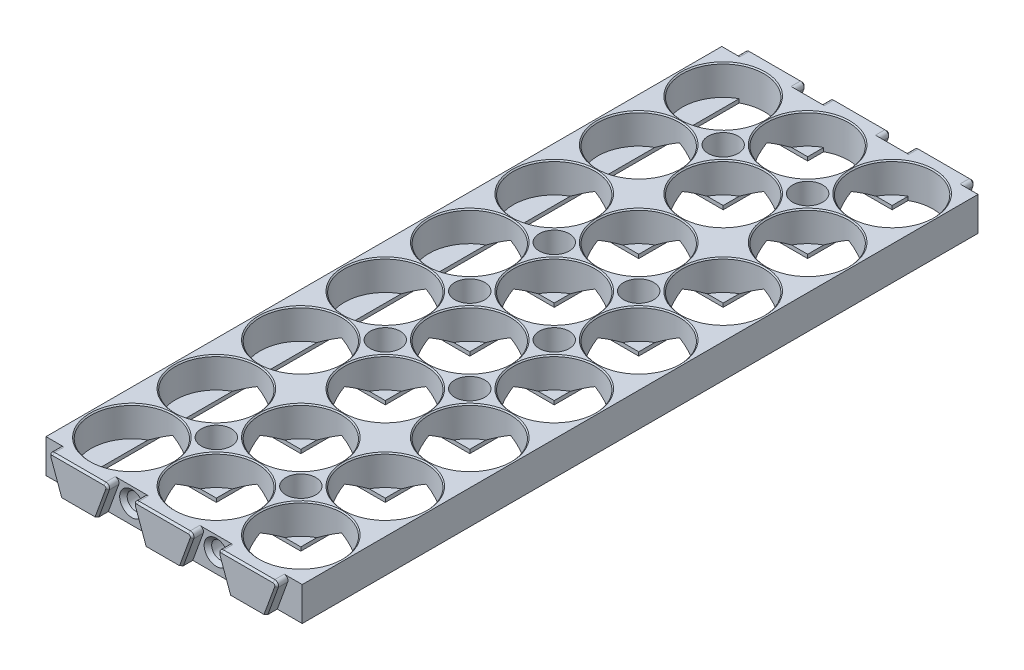
SolidWorks part; units mm, degrees
ref_plane "Front Plane" through (0, 0, 0) normal (0, 0, 1) x (1, 0, 0)
ref_plane "Top Plane" through (0, 0, 0) normal (0, 1, 0) x (1, 0, 0)
ref_plane "Right Plane" through (0, 0, 0) normal (1, 0, 0) x (0, 0, -1)
sketch "Sketch1" plane through (0, 0, 0) normal (0, 1, 0) x (1, 0, 0)
  line L0 (-11.25, 10.875) -> (11.25, 10.875) construction
  line L1 (-11.25, -11.25) -> (11.25, -11.25)
  line L2 (-11.25, -11.25) -> (-11.25, 11.25)
  line L3 (-11.25, 11.25) -> (11.25, 11.25)
  line L4 (11.25, -11.25) -> (11.25, 11.25)
  line L5 (-11.25, -11.25) -> (11.25, 11.25) construction
  line L6 (-11.25, 11.25) -> (11.25, -11.25) construction
  circle A0 centre (0, 0) radius 10.875
  point P0 (0, 0)
  dimension "D1" = 21.75
  dimension "D2" = 22.5
  dimension "D3" = 0.375
extrude "Boss-Extrude1" add sketch "Sketch1" along normal blind 8
sketch "Sketch2" plane through (0, 0, 0) normal (0, -1, 0) x (1, 0, 0)
  line L0 (5.25, 11.25) -> (-5.25, 11.25) construction
  line L1 (11.25, 11.25) -> (5.25, 11.25)
  line L2 (11.25, 11.25) -> (11.25, 5.25)
  line L3 (11.25, 5.25) -> (5.25, 5.25)
  line L4 (5.25, 11.25) -> (5.25, 5.25)
  line L5 (11.25, -11.25) -> (5.25, -11.25)
  line L6 (11.25, -11.25) -> (11.25, -5.25)
  line L7 (11.25, -5.25) -> (5.25, -5.25)
  line L8 (5.25, -11.25) -> (5.25, -5.25)
  line L9 (-11.25, -11.25) -> (-5.25, -11.25)
  line L10 (-11.25, -11.25) -> (-11.25, -5.25)
  line L11 (-11.25, -5.25) -> (-5.25, -5.25)
  line L12 (-5.25, -11.25) -> (-5.25, -5.25)
  line L13 (-11.25, 11.25) -> (-5.25, 11.25)
  line L14 (-11.25, 11.25) -> (-11.25, 5.25)
  line L15 (-11.25, 5.25) -> (-5.25, 5.25)
  line L16 (-5.25, 11.25) -> (-5.25, 5.25)
  line L17 (11.25, 5.25) -> (11.25, -5.25) construction
  line L18 (5.25, -11.25) -> (-5.25, -11.25) construction
  line L19 (-11.25, 5.25) -> (-11.25, -5.25) construction
  dimension "D1" = 10.5
extrude "Boss-Extrude2" add sketch "Sketch2" along normal blind 1
chamfer "Chamfer2" distance 0.3 angle 45 1 edges at (0, 8, 10.875)
pattern_linear "LPattern1" count 8 spacing 22.5 along (0, 0, 1) count 3 spacing 22.5 along (1, 0, 0) of "Boss-Extrude2", "Boss-Extrude1", "Chamfer2"
sketch "Sketch5" plane through (0, 0, -5.25) normal (0, 0, 1) x (1, 0, 0)
  line L25 (-5.25, -1) -> (-5.25, 0) construction
  line L26 (-5.25, -1) -> (-11.25, -1) construction
  line L27 (-11.25, -1) -> (-11.25, 0) construction
  line L29 (-5.25, 0) -> (-9.5238, 0) construction
  line L35 (-5.25, -1) -> (-5.25, 0)
  line L36 (-5.25, -1) -> (-11.25, -1)
  line L37 (-11.25, -1) -> (-11.25, 0)
  line L39 (-5.25, 0) -> (-11.25, 0)
  line L55 (56.25, -1) -> (50.25, -1)
  line L56 (56.25, -1) -> (56.25, 0)
  line L57 (56.25, 0) -> (50.25, 0)
  line L58 (50.25, -1) -> (50.25, 0)
  dimension "D1" = 6
extrude "Boss-Extrude3" add sketch "Sketch5" along normal up to surface (174 mm away)
sketch "Sketch6" plane through (0, 0, 0) normal (0, -1, 0) x (1, 0, 0)
  line L27 (39.75, -11.25) -> (50.25, -11.25) construction
  line L28 (50.25, -11.25) -> (50.25, -9.5238) construction
  line L29 (39.75, -9.5238) -> (39.75, -11.25) construction
  line L30 (17.25, -9.5238) -> (17.25, -11.25) construction
  line L31 (17.25, -11.25) -> (27.75, -11.25) construction
  line L32 (27.75, -11.25) -> (27.75, -9.5238) construction
  line L33 (-5.25, -9.5238) -> (-5.25, -11.25) construction
  line L34 (-5.25, -11.25) -> (5.25, -11.25) construction
  line L35 (5.25, -11.25) -> (5.25, -9.5238) construction
  line L51 (39.75, -11.25) -> (50.25, -11.25)
  line L52 (50.25, -11.25) -> (50.25, -9.5238)
  line L53 (39.75, -9.5238) -> (39.75, -11.25)
  line L54 (17.25, -9.5238) -> (17.25, -11.25)
  line L55 (17.25, -11.25) -> (27.75, -11.25)
  line L56 (27.75, -11.25) -> (27.75, -9.5238)
  line L57 (-5.25, -9.5238) -> (-5.25, -11.25)
  line L58 (-5.25, -11.25) -> (5.25, -11.25)
  line L59 (5.25, -11.25) -> (5.25, -9.5238)
  line L84 (5.25, 168.75) -> (-5.25, 168.75) construction
  line L85 (-5.25, 168.75) -> (-5.25, 167.0238) construction
  line L86 (5.25, 167.0238) -> (5.25, 168.75) construction
  line L87 (27.75, 167.0238) -> (27.75, 168.75) construction
  line L88 (27.75, 168.75) -> (17.25, 168.75) construction
  line L89 (17.25, 168.75) -> (17.25, 167.0238) construction
  line L93 (50.25, 167.0238) -> (50.25, 168.75) construction
  line L94 (50.25, 168.75) -> (39.75, 168.75) construction
  line L95 (39.75, 168.75) -> (39.75, 167.0238) construction
  line L96 (5.25, 168.75) -> (-5.25, 168.75)
  line L97 (-5.25, 168.75) -> (-5.25, 167.0238)
  line L98 (5.25, 167.0238) -> (5.25, 168.75)
  line L99 (27.75, 167.0238) -> (27.75, 168.75)
  line L100 (27.75, 168.75) -> (17.25, 168.75)
  line L101 (17.25, 168.75) -> (17.25, 167.0238)
  line L105 (50.25, 167.0238) -> (50.25, 168.75)
  line L106 (50.25, 168.75) -> (39.75, 168.75)
  line L107 (39.75, 168.75) -> (39.75, 167.0238)
  arc A9 (39.75, -9.5238) -> (50.25, -9.5238) centre (45, 0) ccw construction
  arc A10 (17.25, -9.5238) -> (27.75, -9.5238) centre (22.5, 0) ccw construction
  arc A11 (-5.25, -9.5238) -> (5.25, -9.5238) centre (0, 0) ccw construction
  arc A17 (39.75, -9.5238) -> (50.25, -9.5238) centre (45, 0) ccw
  arc A18 (17.25, -9.5238) -> (27.75, -9.5238) centre (22.5, 0) ccw
  arc A19 (-5.25, -9.5238) -> (5.25, -9.5238) centre (0, 0) ccw
  arc A28 (5.25, 167.0238) -> (-5.25, 167.0238) centre (0, 157.5) ccw construction
  arc A29 (27.75, 167.0238) -> (17.25, 167.0238) centre (22.5, 157.5) ccw construction
  arc A31 (50.25, 167.0238) -> (39.75, 167.0238) centre (45, 157.5) ccw construction
  arc A32 (5.25, 167.0238) -> (-5.25, 167.0238) centre (0, 157.5) ccw
  arc A33 (27.75, 167.0238) -> (17.25, 167.0238) centre (22.5, 157.5) ccw
  arc A35 (50.25, 167.0238) -> (39.75, 167.0238) centre (45, 157.5) ccw
extrude "Boss-Extrude4" add sketch "Sketch6" along normal up to surface (1 mm away) up to face at (-8.25, -1, 78.75)
sketch "Sketch7" plane through (0, 0, 0) normal (0, 0, 1) x (1, 0, 0)
  line L0 (-11.25, 8) -> (56.25, 8) construction
  line L1 (-5.25, 0) -> (5.25, 0)
  line L2 (-5.25, 0) -> (0, 5.25) construction
  line L3 (0, 5.25) -> (5.25, 0) construction
  line L4 (0, 0) -> (0, 8) construction
  line L6 (-5.25, 0) -> (0, 3.0311)
  line L7 (0, 3.0311) -> (5.25, 0)
  line L9 (-5.25, -1) -> (-5.25, 0) construction
  line L10 (5.25, -1) -> (5.25, 0) construction
  line L11 (-5.25, -1) -> (-5.25, 0) construction
  line L12 (5.25, -1) -> (5.25, 0) construction
  line L13 (17.25, 0) -> (22.5, 3.0311)
  line L14 (22.5, 3.0311) -> (27.75, 0)
  line L15 (17.25, 0) -> (27.75, 0)
  line L16 (39.75, 0) -> (45, 3.0311)
  line L17 (45, 3.0311) -> (50.25, 0)
  line L18 (39.75, 0) -> (50.25, 0)
  line L22 (-5.25, 0) -> (17.25, 0) construction
  dimension "D1" = 45
  dimension "D2" = 30
  dimension "D3" = 4.9689
  dimension "D5" = 22.5
  dimension "D4" = 3
extrude "Cut-Extrude1" cut sketch "Sketch7" along normal up to surface (152.25 mm away) up to face at (33.75, -0.3333, 152.25)
sketch "Sketch16" plane through (0, 0, 0) normal (1, 0, 0) x (0, 0, -1)
  line L2 (-5.25, -1) -> (-5.25, 0) construction
  line L3 (5.25, -1) -> (5.25, 0) construction
  line L4 (-5.25, 0) -> (0, 3.0311)
  line L5 (0, 3.0311) -> (5.25, 0)
  line L6 (-5.25, 0) -> (5.25, 0)
  line L7 (-5.25, -1) -> (-5.25, 0) construction
  line L8 (5.25, -1) -> (5.25, 0) construction
  line L9 (-22.5, 3.0311) -> (-17.25, 0)
  line L10 (-27.75, 0) -> (-17.25, 0)
  line L11 (-27.75, 0) -> (-22.5, 3.0311)
  line L12 (-45, 3.0311) -> (-39.75, 0)
  line L13 (-50.25, 0) -> (-39.75, 0)
  line L14 (-50.25, 0) -> (-45, 3.0311)
  line L15 (-67.5, 3.0311) -> (-62.25, 0)
  line L16 (-72.75, 0) -> (-62.25, 0)
  line L17 (-72.75, 0) -> (-67.5, 3.0311)
  line L18 (-90, 3.0311) -> (-84.75, 0)
  line L19 (-95.25, 0) -> (-84.75, 0)
  line L20 (-95.25, 0) -> (-90, 3.0311)
  line L21 (-112.5, 3.0311) -> (-107.25, 0)
  line L22 (-117.75, 0) -> (-107.25, 0)
  line L23 (-117.75, 0) -> (-112.5, 3.0311)
  line L24 (-135, 3.0311) -> (-129.75, 0)
  line L25 (-140.25, 0) -> (-129.75, 0)
  line L26 (-140.25, 0) -> (-135, 3.0311)
  line L27 (-157.5, 3.0311) -> (-152.25, 0)
  line L28 (-162.75, 0) -> (-152.25, 0)
  line L29 (-162.75, 0) -> (-157.5, 3.0311)
  line L42 (0, 3.0311) -> (-22.5, 3.0311) construction
  dimension "D1" = 30
  dimension "D3" = 22.5
  dimension "D2" = 8
extrude "Cut-Extrude7" cut sketch "Sketch16" along normal up to surface (39.75 mm away) up to face at (39.75, -0.5, -7.3869)
sketch "Sketch8" plane through (0, 0, -11.25) normal (0, 0, -1) x (-1, 0, 0)
  line L0 (0, -1) -> (0, 8) construction
  line L1 (-27.4743, -1) -> (-30.75, 8)
  line L2 (-56.25, 8) -> (11.25, 8) construction
  line L3 (4.9743, -1) -> (-4.9743, -1)
  line L4 (-4.9743, -1) -> (-8.25, 8)
  line L5 (-8.25, 8) -> (8.25, 8)
  line L6 (4.9743, -1) -> (8.25, 8)
  line L7 (11.25, 8) -> (11.25, -1) construction
  line L8 (11.25, -1) -> (-56.25, -1) construction
  line L9 (-30.75, 8) -> (-14.25, 8)
  line L10 (-56.25, 8) -> (11.25, 8) construction
  line L11 (-17.5257, -1) -> (-14.25, 8)
  line L12 (-17.5257, -1) -> (-27.4743, -1)
  line L13 (-49.9743, -1) -> (-53.25, 8)
  line L14 (-53.25, 8) -> (-36.75, 8)
  line L15 (-40.0257, -1) -> (-36.75, 8)
  line L16 (-40.0257, -1) -> (-49.9743, -1)
  line L21 (-4.9743, -1) -> (-27.4743, -1) construction
  line L22 (-56.25, 8) -> (11.25, 8) construction
  dimension "D1" = 70
  dimension "D2" = 3
  dimension "D4" = 22.5
  dimension "D5" = 9
  dimension "D3" = 3
sketch "Sketch9" plane through (0, 0, 168.75) normal (0, 0, 1) x (1, 0, 0)
  line L24 (-4.9743, -1) -> (4.9743, -1)
  line L25 (4.9743, -1) -> (8.25, 8)
  line L26 (8.25, 8) -> (-8.25, 8)
  line L27 (-8.25, 8) -> (-4.9743, -1)
  line L28 (-4.9743, -1) -> (4.9743, -1)
  line L29 (4.9743, -1) -> (8.25, 8)
  line L30 (8.25, 8) -> (-8.25, 8)
  line L31 (-8.25, 8) -> (-4.9743, -1)
  line L40 (49.9743, -1) -> (53.25, 8)
  line L41 (53.25, 8) -> (36.75, 8)
  line L42 (36.75, 8) -> (40.0257, -1)
  line L43 (40.0257, -1) -> (49.9743, -1)
  line L44 (49.9743, -1) -> (53.25, 8)
  line L45 (53.25, 8) -> (36.75, 8)
  line L46 (36.75, 8) -> (40.0257, -1)
  line L47 (40.0257, -1) -> (49.9743, -1)
  line L48 (14.25, 8) -> (17.5257, -1)
  line L49 (17.5257, -1) -> (27.4743, -1)
  line L50 (27.4743, -1) -> (30.75, 8)
  line L51 (30.75, 8) -> (14.25, 8)
  line L52 (14.25, 8) -> (17.5257, -1)
  line L53 (17.5257, -1) -> (27.4743, -1)
  line L54 (27.4743, -1) -> (30.75, 8)
  line L55 (30.75, 8) -> (14.25, 8)
  dimension "D1" = 0
  dimension "D3" = 0
  dimension "D4" = 0
extrude "Boss-Extrude5" add sketch "Sketch8" along normal blind 3
extrude "Boss-Extrude6" add sketch "Sketch9" along normal blind 3
fillet "Fillet1" radius 1 12 edges at (-8.25, 8, -12.75) (36.75, 8, -12.75) (30.75, 8, -12.75) (8.25, 8, -12.75) (14.25, 8, -12.75) (53.25, 8, -12.75) (-8.25, 8, 170.25) (8.25, 8, 170.25) (14.25, 8, 170.25) (30.75, 8, 170.25) (36.75, 8, 170.25) (53.25, 8, 170.25)
chamfer "Chamfer3" distance 0.5 angle 45 30 edges at (6.3679, 2.829, -14.25) (0, 8, -14.25) (-6.3679, 2.829, -14.25) (51.3679, 2.829, -14.25) (45, 8, -14.25) (38.6321, 2.829, -14.25) (28.8679, 2.829, -14.25) (22.5, 8, -14.25) (16.1321, 2.829, -14.25) (51.3679, 2.829, 171.75) (38.6321, 2.829, 171.75) (45, 8, 171.75) (28.8679, 2.829, 171.75) (16.1321, 2.829, 171.75) (22.5, 8, 171.75) (6.3679, 2.829, 171.75) (-6.3679, 2.829, 171.75) (0, 8, 171.75) (52.641, 7.5736, 171.75) (37.359, 7.5736, 171.75) (30.141, 7.5736, 171.75) (14.859, 7.5736, 171.75) (7.641, 7.5736, 171.75) (-7.641, 7.5736, 171.75) (52.641, 7.5736, -14.25) (37.359, 7.5736, -14.25) (30.141, 7.5736, -14.25) (14.859, 7.5736, -14.25) (7.641, 7.5736, -14.25) (-7.641, 7.5736, -14.25)
sketch "Sketch10" plane through (0, 0, -11.25) normal (0, 0, -1) x (-1, 0, 0)
  line L0 (-11.25, -1) -> (-11.25, 8) construction
  line L1 (-26.9422, -1) -> (-18.0578, -1) construction
  line L2 (-4.9743, -1) -> (-17.5257, -1) construction
  line L3 (-29.3219, 8) -> (-15.6781, 8) construction
  line L4 (-14.25, 8) -> (-8.25, 8) construction
  line L5 (-22.5, 8) -> (-22.5, -1) construction
  circle A0 centre (-11.25, 4) radius 2.25
  circle A1 centre (-33.75, 4) radius 2.25
  dimension "D2" = 4.5
  dimension "D1" = 4
sketch "Sketch11" plane through (0, 0, 168.75) normal (0, 0, 1) x (1, 0, 0)
  circle A0 centre (11.25, 4) radius 2.25 construction
  circle A1 centre (11.25, 4) radius 2.25
  circle A2 centre (33.75, 4) radius 2.25 construction
  circle A3 centre (33.75, 4) radius 2.25
extrude "Cut-Extrude2" cut sketch "Sketch10" against normal blind 5
extrude "Cut-Extrude3" cut sketch "Sketch11" against normal blind 5
chamfer "Chamfer5" distance 1 angle 45 4 edges at (36, 4, -11.25) (9, 4, -11.25) (13.5, 4, 168.75) (36, 4, 168.75)
sketch "Sketch17" plane through (0, -1, 0) normal (0, -1, 0) x (1, 0, 0)
  line L0 (5.25, 5.25) -> (17.25, 17.25) construction
  line L1 (11.25, 11.25) -> (33.75, 11.25) construction
  circle A0 centre (11.25, 11.25) radius 4
  circle A1 centre (33.75, 11.25) radius 4
  circle A33 centre (33.75, 146.25) radius 4 [skipped]
  circle A35 centre (33.75, 168.75) radius 4 [skipped]
  circle A36 centre (33.75, 191.25) radius 4 [skipped]
  circle A38 centre (33.75, 213.75) radius 4 [skipped]
  circle A40 centre (33.75, 236.25) radius 4 [skipped]
  circle A42 centre (11.25, 146.25) radius 4 [skipped]
  circle A43 centre (11.25, 191.25) radius 4 [skipped]
  circle A44 centre (11.25, 213.75) radius 4 [skipped]
  circle A45 centre (11.25, 236.25) radius 4 [skipped]
  circle A47 centre (11.25, 168.75) radius 4 construction
  circle A48 centre (33.75, 123.75) radius 4 [skipped]
  circle A50 centre (11.25, 123.75) radius 4 [skipped]
  circle A57 centre (33.75, 33.75) radius 4 [skipped]
  circle A58 centre (33.75, 56.25) radius 4 [skipped]
  circle A60 centre (33.75, 78.75) radius 4 [skipped]
  circle A62 centre (33.75, 101.25) radius 4 [skipped]
  circle A64 centre (11.25, 56.25) radius 4 [skipped]
  circle A65 centre (11.25, 78.75) radius 4 [skipped]
  circle A66 centre (11.25, 101.25) radius 4 [skipped]
  circle A68 centre (11.25, 33.75) radius 4 construction
  circle A69 centre (11.25, 33.75) radius 4 construction
  circle A70 centre (33.75, 33.75) radius 4 construction
  circle A72 centre (11.25, 56.25) radius 4
  circle A73 centre (33.75, 56.25) radius 4
  circle A75 centre (11.25, 78.75) radius 4
  circle A76 centre (33.75, 78.75) radius 4
  circle A78 centre (11.25, 101.25) radius 4
  circle A79 centre (33.75, 101.25) radius 4
  circle A81 centre (11.25, 123.75) radius 4 construction
  circle A82 centre (33.75, 123.75) radius 4 construction
  circle A84 centre (11.25, 146.25) radius 4
  circle A85 centre (33.75, 146.25) radius 4
  circle A87 centre (11.25, 258.75) radius 4 [skipped]
  circle A88 centre (33.75, 258.75) radius 4 [skipped]
  circle A89 centre (11.25, 281.25) radius 4 [skipped]
  circle A90 centre (33.75, 281.25) radius 4 [skipped]
  dimension "D4" = 22.5
  dimension "D1" = 8
  dimension "D6" = 22.5
  dimension "D3" = 13
  dimension "D5" = 7
extrude "Cut-Extrude8" cut sketch "Sketch17" against normal through all
sketch "Sketch18" plane through (0, -1, 0) normal (0, -1, 0) x (1, 0, 0)
  line L2 (5.25, 117.75) -> (17.25, 129.75) construction
  line L3 (5.25, 27.75) -> (17.25, 39.75) construction
  line L4 (27.75, 27.75) -> (39.75, 39.75) construction
  line L5 (27.75, 27.75) -> (39.75, 27.75) construction
  line L6 (27.75, 39.75) -> (27.75, 27.75) construction
  line L7 (56.25, -11.25) -> (56.25, 168.75) construction
  line L8 (39.75, 117.75) -> (39.75, 129.75) construction
  line L9 (39.75, 129.75) -> (27.75, 129.75) construction
  line L38 (56.25, 78.75) -> (-11.25, 78.75) construction
  line L40 (-11.25, 168.75) -> (-11.25, -11.25) construction
  line L42 (27.75, 117.75) -> (39.75, 129.75) construction
  circle A0 centre (11.25, 33.75) radius 2.1
  circle A4 centre (33.75, 33.75) radius 2.1
  circle A7 centre (33.75, 123.75) radius 2.1
  circle A8 centre (11.25, 123.75) radius 2.1
  dimension "D1" = 4.2
extrude "Cut-Extrude9" cut sketch "Sketch18" against normal blind 4
sketch "Sketch19" plane through (0, -1, 0) normal (0, -1, 0) x (1, 0, 0)
  line L0 (56.25, 78.75) -> (-11.25, 78.75) construction
  line L2 (-11.25, 168.75) -> (-11.25, -11.25) construction
  line L3 (56.25, -11.25) -> (56.25, 168.75) construction
  circle A2 centre (33.75, 123.75) radius 1.7
  circle A3 centre (11.25, 33.75) radius 1.7
  circle A4 centre (11.25, 123.75) radius 1.7
  circle A5 centre (33.75, 33.75) radius 1.7
  dimension "D1" = 3.4
extrude "Cut-Extrude10" cut sketch "Sketch19" against normal offset from surface (7 mm away) 2 up to face at (33.75, 8, 74.75)
chamfer "Chamfer6" distance 1 angle 45 4 edges at (11.25, -1, 121.65) (11.25, -1, 31.65) (33.75, -1, 121.65) (33.75, -1, 31.65)
sketch "Sketch22" plane through (0, 8, 0) normal (0, 1, 0) x (1, 0, 0)
  line L0 (-11.25, -168.75) -> (-6.8219, -168.75) construction
  line L1 (-11.25, 11.25) -> (-11.625, 11.25)
  line L2 (-11.25, 11.25) -> (-11.25, -168.75)
  line L3 (-11.25, -168.75) -> (-11.625, -168.75)
  line L4 (-11.625, 11.25) -> (-11.625, -168.75)
  line L5 (22.5, 14.25) -> (22.5, -171.75) construction
  line L12 (29.3219, -171.75) -> (15.6781, -171.75) construction
  line L13 (15.6781, 14.25) -> (29.3219, 14.25) construction
  line L14 (56.625, 11.25) -> (56.625, -168.75)
  line L15 (56.25, -168.75) -> (56.625, -168.75)
  line L16 (56.25, 11.25) -> (56.25, -168.75)
  line L17 (56.25, 11.25) -> (56.625, 11.25)
  arc A1 (-5.25, 9.5238) -> (-5.25, -9.5238) centre (0, 0) ccw construction
  point P10 (-10.875, 0)
  dimension "D1" = 0.75
  dimension "D2" = 0.375
extrude "Boss-Extrude7" add sketch "Sketch22" against normal up to surface (9 mm away) up to face at (22.5, -1, 78.75)
sketch "Sketch14" plane through (0, -1, 0) normal (0, -1, 0) x (1, 0, 0)
  line L0 (-10.25, 76.2941) -> (-10.25, 81.2059)
  line L2 (-6.25, 77.75) -> (-6.25, 79.75)
  line L3 (18.0578, 171.75) -> (26.9422, 171.75) construction
  line L4 (-11.625, -11.25) -> (-11.625, 168.75) construction
  line L19 (-5.25, 11.25) -> (-11.625, 11.25) construction
  line L30 (-5.25, 9.5238) -> (-5.25, 12.9762) construction
  line L39 (-6.25, 10.25) -> (-6.25, 12.25)
  line L51 (-10.25, 8.7941) -> (-10.25, 13.7059)
  line L52 (-10.25, 13.7059) -> (-6.25, 12.25)
  line L53 (22.5, -14.25) -> (22.5, 171.75) construction
  line L56 (-5.25, 146.25) -> (-11.625, 146.25) construction
  line L58 (-5.25, -9.5238) -> (-5.25, 167.0238) construction
  line L59 (-10.25, 81.2059) -> (-6.25, 79.75)
  line L60 (-5.25, 78.75) -> (-11.625, 78.75) construction
  line L61 (-10.25, 148.7059) -> (-6.25, 147.25)
  line L64 (-10.25, 143.7941) -> (-6.25, 145.25)
  line L65 (-10.25, 148.7059) -> (-10.25, 143.7941)
  line L66 (-6.25, 147.25) -> (-6.25, 145.25)
  line L67 (50.25, 78.75) -> (56.625, 78.75) construction
  line L68 (26.9422, -14.25) -> (18.0578, -14.25) construction
  line L69 (50.25, 146.25) -> (56.625, 146.25) construction
  line L70 (50.25, 11.25) -> (56.625, 11.25) construction
  line L71 (55.25, 76.2941) -> (51.25, 77.75)
  line L75 (-10.25, 8.7941) -> (-6.25, 10.25)
  line L76 (55.25, 8.7941) -> (51.25, 10.25)
  line L77 (51.25, 147.25) -> (51.25, 145.25)
  line L78 (55.25, 148.7059) -> (55.25, 143.7941)
  line L79 (55.25, 143.7941) -> (51.25, 145.25)
  line L84 (55.25, 148.7059) -> (51.25, 147.25)
  line L85 (55.25, 81.2059) -> (51.25, 79.75)
  line L86 (55.25, 13.7059) -> (51.25, 12.25)
  line L87 (55.25, 8.7941) -> (55.25, 13.7059)
  line L95 (-10.25, 76.2941) -> (-6.25, 77.75)
  line L96 (51.25, 10.25) -> (51.25, 12.25)
  line L97 (51.25, 77.75) -> (51.25, 79.75)
  line L98 (55.25, 76.2941) -> (55.25, 81.2059)
  point P0 (-10.25, 146.25)
  point P2 (-10.25, 78.75)
  point P8 (-6.25, 11.25)
  point P11 (-10.25, 11.25)
  point P31 (-6.25, 78.75)
  point P32 (-6.25, 146.25)
  point P54 (51.25, 146.25)
  point P55 (51.25, 78.75)
  point P56 (55.25, 11.25)
  point P57 (51.25, 11.25)
  point P58 (55.25, 78.75)
  point P59 (55.25, 146.25)
  dimension "D1" = 70
  dimension "D2" = 1
  dimension "D3" = 1.375
  dimension "D4" = 4
  dimension "D5" = 70
  dimension "D7" = 4
  dimension "D8" = 1
extrude "Cut-Extrude11" cut sketch "Sketch14" against normal blind 2
chamfer "Chamfer7" distance 0.5 angle 45 24 edges at (-10.25, -1, 146.25) (-8.25, -1, 144.5221) (-6.25, -1, 146.25) (-8.25, -1, 147.9779) (51.25, -1, 146.25) (53.25, -1, 144.5221) (55.25, -1, 146.25) (53.25, -1, 147.9779) (-8.25, -1, 77.0221) (-6.25, -1, 78.75) (-10.25, -1, 78.75) (-8.25, -1, 80.4779) (55.25, -1, 78.75) (53.25, -1, 77.0221) (51.25, -1, 78.75) (53.25, -1, 80.4779) (55.25, -1, 11.25) (53.25, -1, 9.5221) (51.25, -1, 11.25) (53.25, -1, 12.9779) (-6.25, -1, 11.25) (-8.25, -1, 9.5221) (-10.25, -1, 11.25) (-8.25, -1, 12.9779)
equation "\"cell_side\"=22.5"
equation "\"D2@Sketch1\"=\"cell_side\""
equation "\"D5@Sketch7\"=\"cell_side\""
equation "\"D3@Sketch16\"=\"cell_side\""
equation "\"D4@Sketch8\"=\"cell_side\""
equation "\"D3@LPattern1\"=\"cell_side\""
equation "\"D4@LPattern1\"=\"cell_side\""
equation "\"D4@Sketch17\"=\"cell_side\""
